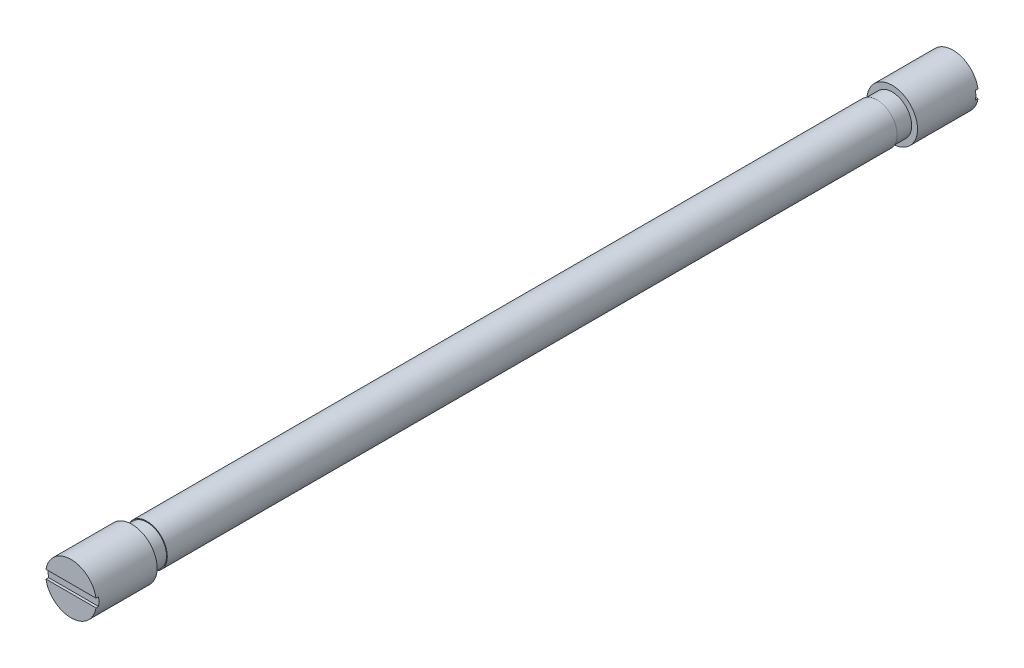
SolidWorks part; units mm, degrees
material "1.4301 (X5CrNi18-10)"
ref_plane "Plan de face" through (0, 0, 0) normal (0, 0, 1) x (1, 0, 0)
ref_plane "Plan de dessus" through (0, 0, 0) normal (0, 1, 0) x (1, 0, 0)
ref_plane "Plan de droite" through (0, 0, 0) normal (1, 0, 0) x (0, 0, -1)
sketch "Esquisse2" plane through (0, 0, 0) normal (1, 0, 0) x (0, 0, -1)
  line L0 (-75, 0) -> (-87, 0)
  line L1 (-51, 0) -> (51, 0)
  line L2 (0, 0) -> (0, 4)
  line L3 (-51, 4) -> (51, 4)
  line L4 (51, 0) -> (51, 4)
  line L5 (51, 0) -> (72, 0)
  line L6 (51, 0) -> (51, 4)
  line L7 (51, 4) -> (72, 4)
  line L8 (72, 0) -> (72, 4)
  line L9 (72, 0) -> (75, 0)
  line L10 (72, 0) -> (72, 3.85)
  line L11 (72, 3.85) -> (75, 3.85)
  line L12 (75, 0) -> (75, 3.85)
  line L13 (75, 0) -> (87, 0)
  line L14 (75, 0) -> (75, 5)
  line L15 (75, 5) -> (87, 5)
  line L16 (87, 0) -> (87, 5)
  line L17 (-87, 0) -> (-87, 5)
  line L18 (-75, 0) -> (-75, 5)
  line L19 (-72, 0) -> (-72, 4)
  line L20 (-75, 5) -> (-87, 5)
  line L21 (-75, 0) -> (-75, 3.85)
  line L22 (-72, 0) -> (-75, 0)
  line L23 (-72, 3.85) -> (-75, 3.85)
  line L24 (-51, 0) -> (-72, 0)
  line L25 (-51, 4) -> (-72, 4)
  line L26 (-51, 0) -> (-51, 4)
  dimension "D1" = 51
  dimension "D2" = 4
  dimension "D3" = 21
  dimension "D4" = 4
  dimension "D5" = 3
  dimension "D6" = 12
  dimension "D7" = 3.85
  dimension "D8" = 5
revolve "Révolution1" add sketch "Esquisse2" angle 360 about L1 region at (0, 1.925, 73.5) region at (0, 2, 61.5) region at (0, 2, 25.5) region at (0, 2, -25.5) region at (0, 2, -61.5) region at (0, 1.925, -73.5) region at (0, 2.5, -81)
sketch "Esquisse4" plane through (0, 0, -87) normal (0, 0, -1) x (-1, 0, 0)
  line L1 (-5.8333, -0.8316) -> (5.8333, -0.8316)
  line L2 (-5.8333, -0.8316) -> (-5.8333, 0.8316)
  line L3 (-5.8333, 0.8316) -> (5.8333, 0.8316)
  line L4 (5.8333, -0.8316) -> (5.8333, 0.8316)
  line L5 (-5.8333, -0.8316) -> (5.8333, 0.8316) construction
  line L6 (-5.8333, 0.8316) -> (5.8333, -0.8316) construction
  point P0 (0, 0)
extrude "Enlèv. mat.-Extru.2" cut sketch "Esquisse4" against normal blind 0.5
mirror "Symétrie2" about plane through (0, 0, 0) normal (0, 0, 1) of "Enlèv. mat.-Extru.2"
